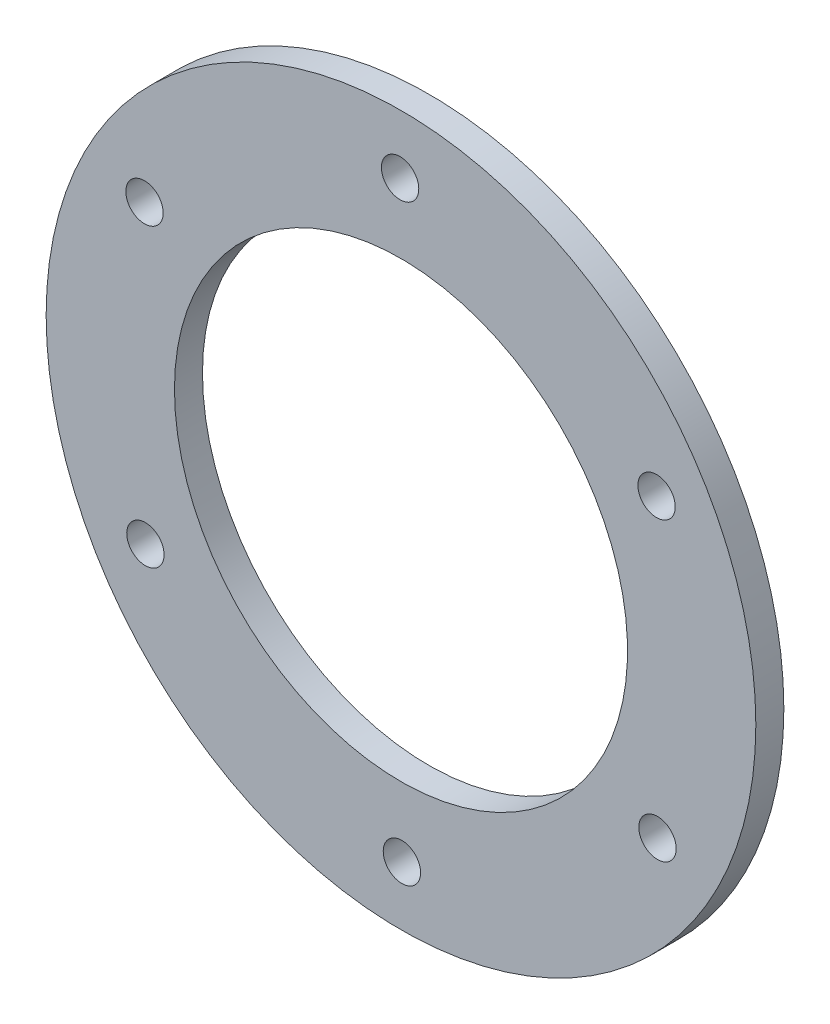
SolidWorks part; units mm, degrees
material "Plain Carbon Steel"
ref_plane "Front Plane" through (0, 0, 0) normal (0, 0, 1) x (1, 0, 0)
ref_plane "Top Plane" through (0, 0, 0) normal (0, 1, 0) x (1, 0, 0)
ref_plane "Right Plane" through (0, 0, 0) normal (1, 0, 0) x (0, 0, -1)
sketch "Sketch1" plane through (0, 0, 0) normal (0, 0, 1) x (1, 0, 0)
  circle A0 centre (-1180.802, 3304.6244) radius 77.0255
  circle A1 centre (-1180.802, 3304.6244) radius 120.65
  dimension "D1" = 241.3
extrude "Extrude1" add sketch "Sketch1" along normal blind 9.525
hole_wizard "1/2 (0.5) Diameter Hole1" positions "3DSketch1" profile "Sketch2" hole size "1/2" standard "Ansi Inch"
sketch3d "3DSketch1"
  line L3 (-1181.11, 3381.6493, 9.525) -> (-1181.11, 3425.274, 9.525) construction
  circle A1 centre (-1180.802, 3304.6244, 9.525) radius 77.0255 construction
  circle A2 centre (-1180.802, 3304.6244, 9.525) radius 120.65 construction
  point P0 (-1181.11, 3405.1443, 9.525)
  point P18 (-1180.802, 3304.6244, 86.5505)
  point P28 (-1180.802, 3304.6244, 130.175)
sketch "Sketch2" plane through (-1181.11, 3405.1443, 9.525) normal (1, 0, 0) x (0, -1, 0)
  line L0 (0, 0) -> (0, 29.2155)
  line L1 (0, 29.2155) -> (6.35, 25.4)
  line L2 (6.35, 25.4) -> (6.35, 0)
  line L5 (6.35, 0) -> (0, 0)
  line L10 (0, 29.2155) -> (-6.35, 25.4) construction
  line L11 (0, -6.35) -> (0, 107.95) construction
  dimension "Hole Dia." = 12.7
  dimension "Hole Depth" = 25.4
  dimension "Drill Angle" = 118
pattern_circular "CirPattern1" count 6 over 360 of "1/2 (0.5) Diameter Hole1" reverse direction yes
